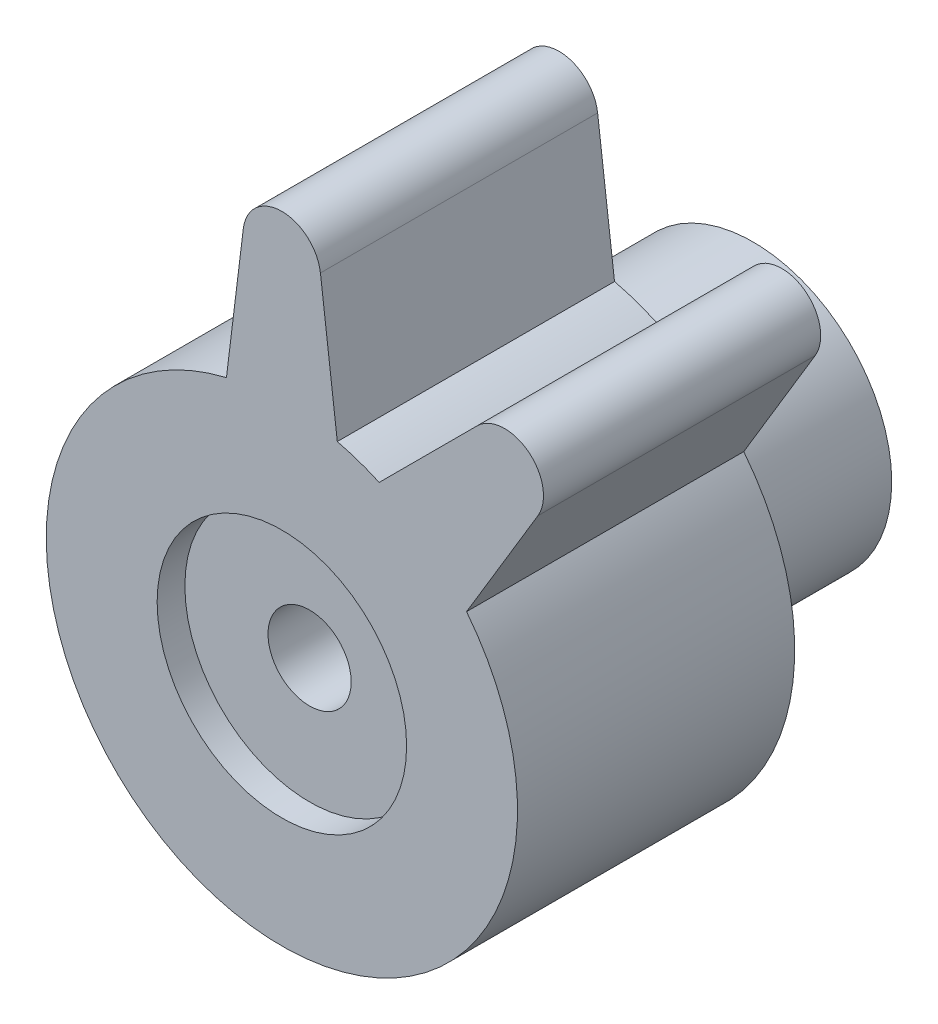
SolidWorks part; units mm, degrees
ref_plane "Front Plane" through (0, 0, 0) normal (0, 0, 1) x (1, 0, 0)
ref_plane "Top Plane" through (0, 0, 0) normal (0, 1, 0) x (1, 0, 0)
ref_plane "Right Plane" through (0, 0, 0) normal (1, 0, 0) x (0, 0, -1)
sketch "Sketch1" plane through (0, 0, 0) normal (0, 0, 1) x (1, 0, 0)
  line L0 (0, 0) -> (0, 51.188) construction
  line L1 (-2, 8.2614) -> (-1.3907, 13.2241)
  line L2 (2, 8.2614) -> (1.3907, 13.2241)
  line L3 (0, 0) -> (22.4184, 65.1077) construction
  line L4 (6.6622, 5.2787) -> (9.2374, 9.5646)
  line L5 (0, 0) -> (31.5145, 40.3367) construction
  line L6 (3.5102, 7.7414) -> (7.0457, 11.2769)
  circle A0 centre (0, 0) radius 8.5
  circle A1 centre (0, 0) radius 1.5
  arc A2 (-1.3907, 13.2241) -> (1.3907, 13.2241) centre (0, 13.0533) cw
  arc A3 (9.2374, 9.5646) -> (7.0457, 11.2769) centre (8.0364, 10.2862) ccw
  circle A4 centre (0, 0) radius 12 construction
  dimension "D1" = 24
  dimension "D2" = 17
  dimension "D3" = 3
  dimension "D4" = 7
  dimension "D7" = 5
  dimension "D5" = 4
  dimension "D6" = 19
extrude "Boss-Extrude1" add sketch "Sketch1" along normal blind 10 contours A0 A1 | A2 L1 A0 L2 | A0 region at (0, 11.1065, 0) region at (0, 8.2596, 0) region at (6.8378, 8.752, 0)
sketch "Sketch5" plane through (0, 0, 0) normal (0, 0, -1) x (-1, 0, 0)
  line L0 (1.95, -2.6) -> (-1.95, -2.6)
  circle A0 centre (0, 0) radius 3.25
  circle A1 centre (0, 0) radius 5
  dimension "D1" = 10
  dimension "D2" = 6.5
  dimension "D3" = 2.6
extrude "Boss-Extrude3" add sketch "Sketch5" along normal blind 7 contours A1 A0 | L0 A0 region at (0, -2.8624, 0) region at (4.8586, 0, 0)
sketch "Sketch8" plane through (0, 0, 10) normal (0, 0, 1) x (1, 0, 0)
  circle A0 centre (0, 0) radius 4.5
  dimension "D1" = 9
extrude "Cut-Extrude2" cut sketch "Sketch8" against normal blind 1
